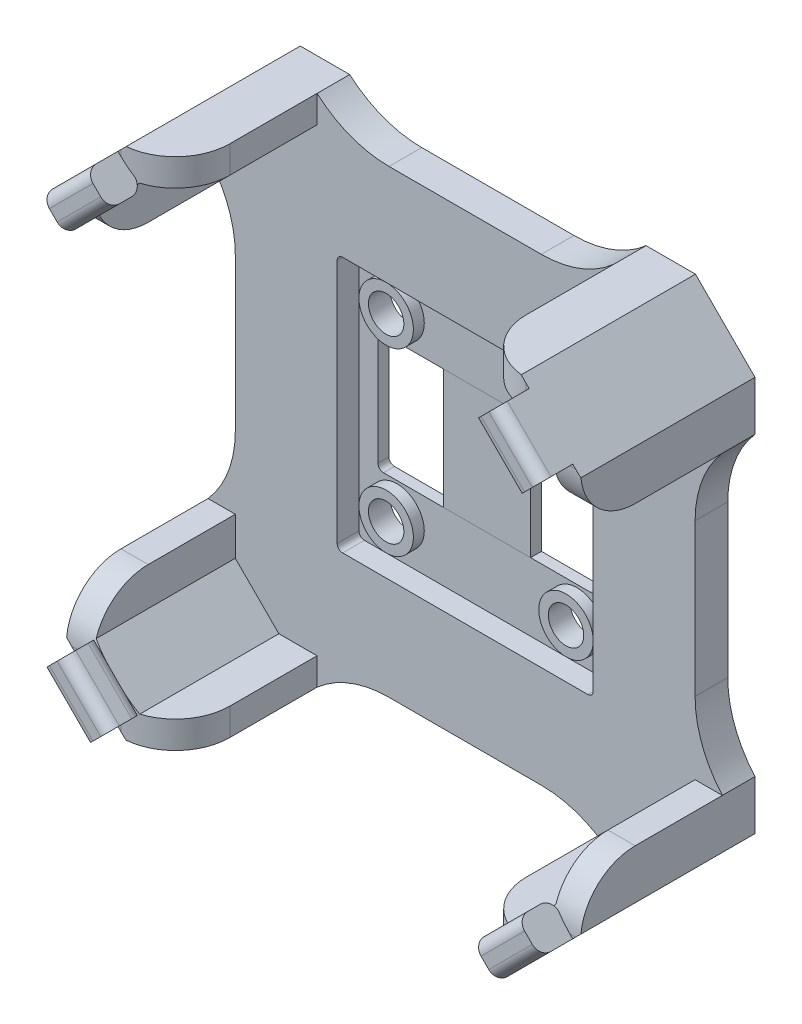
SolidWorks part; units mm, degrees
ref_plane "Front Plane" through (0, 0, 0) normal (0, 0, 1) x (1, 0, 0)
ref_plane "Top Plane" through (0, 0, 0) normal (0, 1, 0) x (1, 0, 0)
ref_plane "Right Plane" through (0, 0, 0) normal (1, 0, 0) x (0, 0, -1)
sketch "Sketch1" plane through (0, 0, 0) normal (0, 0, 1) x (1, 0, 0)
  line L1 (-21.1, 21.1) -> (21.1, 21.1)
  line L2 (-21.1, 21.1) -> (-21.1, -21.1)
  line L3 (-21.1, -21.1) -> (21.1, -21.1)
  line L4 (21.1, 21.1) -> (21.1, -21.1)
  line L5 (0, -21.1) -> (0, 21.1) construction
  line L6 (-21.1, 0) -> (21.1, 0) construction
  line L7 (-10, 5.5) -> (10, 5.5)
  line L8 (-10, 5.5) -> (-10, -5.5)
  line L9 (-10, -5.5) -> (10, -5.5)
  line L10 (10, 5.5) -> (10, -5.5)
  line L11 (0, -5.5) -> (0, 5.5) construction
  line L12 (-10, 0) -> (10, 0) construction
  point P0 (0, 0)
  point P4 (0, 0)
  dimension "D1" = 42.2
  dimension "D2" = 42.2
  dimension "D3" = 20
  dimension "D4" = 11
extrude "Boss-Extrude1" add sketch "Sketch1" along normal blind 3
sketch "Sketch2" plane through (0, 0, 3) normal (0, 0, 1) x (1, 0, 0)
  line L1 (-11.75, 11.75) -> (11.75, 11.75)
  line L2 (-11.75, 11.75) -> (-11.75, -11.75)
  line L3 (-11.75, -11.75) -> (11.75, -11.75)
  line L4 (11.75, 11.75) -> (11.75, -11.75)
  line L5 (0, -11.75) -> (0, 11.75) construction
  line L6 (-11.75, 0) -> (11.75, 0) construction
  point P0 (0, 0)
  dimension "D1" = 23.5
  dimension "D2" = 23.5
extrude "Cut-Extrude1" cut sketch "Sketch2" against normal blind 2
sketch "Sketch3" plane through (0, 0, 0) normal (0, 0, -1) x (-1, 0, 0)
  line L0 (17.1, -21.1) -> (21.1, -17.1)
  line L1 (21.1, -21.1) -> (-21.1, -21.1) construction
  line L2 (21.1, 21.1) -> (21.1, -21.1) construction
  line L4 (21.1, -17.1) -> (21.1, -21.1)
  line L5 (21.1, -21.1) -> (17.1, -21.1)
  line L6 (-21.1, -17.1) -> (-17.1, -21.1)
  line L7 (-17.1, -21.1) -> (-21.1, -21.1)
  line L8 (-21.1, -21.1) -> (-21.1, -17.1)
  line L9 (-17.1, 21.1) -> (-21.1, 17.1)
  line L10 (-21.1, 17.1) -> (-21.1, 21.1)
  line L11 (-21.1, 21.1) -> (-17.1, 21.1)
  line L12 (21.1, 17.1) -> (17.1, 21.1)
  line L13 (17.1, 21.1) -> (21.1, 21.1)
  line L14 (21.1, 21.1) -> (21.1, 17.1)
  point P6 (0, 0)
  dimension "D1" = 4
  dimension "D2" = 5.6569
extrude "Cut-Extrude2" cut sketch "Sketch3" against normal blind 10
sketch "Sketch4" plane through (0, 0, 0) normal (0, 0, -1) x (-1, 0, 0)
  line L0 (21.1, -17.1) -> (21.1, -13.6)
  line L1 (21.1, 17.1) -> (21.1, -17.1) construction
  line L2 (21.1, -13.6) -> (23.6, -13.6)
  line L3 (23.6, -13.6) -> (23.6, -18.1355)
  line L4 (23.6, -18.1355) -> (18.1355, -23.6)
  line L5 (18.1355, -23.6) -> (13.6, -23.6)
  line L6 (13.6, -23.6) -> (13.6, -21.1)
  line L7 (17.1, -21.1) -> (-17.1, -21.1) construction
  line L8 (21.1, -17.1) -> (17.1, -21.1) construction
  line L9 (13.6, -21.1) -> (17.1, -21.1)
  line L10 (21.1, -17.1) -> (17.1, -21.1)
  line L11 (-17.1, -21.1) -> (-13.6, -21.1)
  line L12 (-13.6, -21.1) -> (-13.6, -23.6)
  line L13 (-13.6, -23.6) -> (-18.1355, -23.6)
  line L14 (-18.1355, -23.6) -> (-23.6, -18.1355)
  line L15 (-23.6, -18.1355) -> (-23.6, -13.6)
  line L16 (-23.6, -13.6) -> (-21.1, -13.6)
  line L17 (-21.1, -13.6) -> (-21.1, -17.1)
  line L18 (-17.1, -21.1) -> (-21.1, -17.1)
  line L19 (-21.1, 17.1) -> (-21.1, 13.6)
  line L20 (-21.1, 13.6) -> (-23.6, 13.6)
  line L21 (-23.6, 13.6) -> (-23.6, 18.1355)
  line L22 (-23.6, 18.1355) -> (-18.1355, 23.6)
  line L23 (-18.1355, 23.6) -> (-13.6, 23.6)
  line L24 (-13.6, 23.6) -> (-13.6, 21.1)
  line L25 (-13.6, 21.1) -> (-17.1, 21.1)
  line L26 (-21.1, 17.1) -> (-17.1, 21.1)
  line L27 (17.1, 21.1) -> (13.6, 21.1)
  line L28 (13.6, 21.1) -> (13.6, 23.6)
  line L29 (13.6, 23.6) -> (18.1355, 23.6)
  line L30 (18.1355, 23.6) -> (23.6, 18.1355)
  line L31 (23.6, 18.1355) -> (23.6, 13.6)
  line L32 (23.6, 13.6) -> (21.1, 13.6)
  line L33 (21.1, 13.6) -> (21.1, 17.1)
  line L34 (17.1, 21.1) -> (21.1, 17.1)
  dimension "D1" = 3.5
  dimension "D2" = 2.5
  dimension "D3" = 2.5
  dimension "D4" = 4
extrude "Boss-Extrude2" add sketch "Sketch4" against normal blind 16
fillet "Fillet1" radius 10 8 edges at (-21.1, 13.6, 1.5) (-21.1, -13.6, 1.5) (-13.6, 21.1, 1.5) (13.6, 21.1, 1.5) (21.1, 13.6, 1.5) (21.1, -13.6, 1.5) (13.6, -21.1, 1.5) (-13.6, -21.1, 1.5)
sketch "Sketch5" plane through (0, 0, 1) normal (0, 0, 1) x (1, 0, 0)
  line L0 (6.63, -8.255) -> (-6.63, -8.255) construction
  line L1 (8.255, -6.63) -> (8.255, 6.63) construction
  line L2 (0, -8.255) -> (0, 0) construction
  line L3 (0, 0) -> (8.255, 0) construction
  circle A0 centre (8.255, -8.255) radius 1.625
  circle A1 centre (-8.255, -8.255) radius 1.625
  circle A2 centre (-8.255, 8.255) radius 1.625
  circle A3 centre (8.255, 8.255) radius 1.625
  dimension "D1" = 3.25
  dimension "D3" = 13.26
  dimension "D2" = 4
extrude "Cut-Extrude3" cut sketch "Sketch5" against normal blind 16
sketch "Sketch6" plane through (0, 0, 16) normal (0, 0, 1) x (1, 0, 0)
  line L0 (18.8678, 22.8678) -> (16.7464, 20.7464)
  line L1 (16.7464, 20.7464) -> (20.7464, 16.7464)
  line L2 (20.7464, 16.7464) -> (22.8678, 18.8678)
  line L3 (18.1355, 23.6) -> (23.6, 18.1355) construction
  line L6 (17.1, 21.1) -> (21.1, 17.1) construction
  line L7 (18.8678, 22.8678) -> (22.8678, 18.8678)
  line L8 (21.1, 17.1) -> (17.1, 21.1) construction
  line L9 (22.8678, -18.8678) -> (20.7464, -16.7464)
  line L10 (20.7464, -16.7464) -> (16.7464, -20.7464)
  line L11 (16.7464, -20.7464) -> (18.8678, -22.8678)
  line L12 (22.8678, -18.8678) -> (18.8678, -22.8678)
  line L13 (-18.8678, -22.8678) -> (-16.7464, -20.7464)
  line L14 (-16.7464, -20.7464) -> (-20.7464, -16.7464)
  line L15 (-20.7464, -16.7464) -> (-22.8678, -18.8678)
  line L16 (-18.8678, -22.8678) -> (-22.8678, -18.8678)
  line L17 (-22.8678, 18.8678) -> (-20.7464, 16.7464)
  line L18 (-20.7464, 16.7464) -> (-16.7464, 20.7464)
  line L19 (-16.7464, 20.7464) -> (-18.8678, 22.8678)
  line L20 (-22.8678, 18.8678) -> (-18.8678, 22.8678)
  dimension "D1" = 0.5
  dimension "D2" = 4
extrude "Boss-Extrude3" add sketch "Sketch6" along normal blind 3
fillet "Fillet2" radius 1 4 edges at (18.7464, 18.7464, 16) (-18.7464, 18.7464, 16) (-18.7464, -18.7464, 16) (18.7464, -18.7464, 16)
fillet "Fillet3" radius 5 8 edges at (-22.35, 13.6, 16) (-13.6, 22.35, 16) (-22.35, -13.6, 16) (-13.6, -22.35, 16) (13.6, -22.35, 16) (22.35, -13.6, 16) (22.35, 13.6, 16) (13.6, 22.35, 16)
fillet "Fillet4" radius 1 8 edges at (18.7464, -18.7464, 19) (20.8678, -20.8678, 19) (20.8678, 20.8678, 19) (18.7464, 18.7464, 19) (-18.7464, 18.7464, 19) (-20.8678, 20.8678, 19) (-18.7464, -18.7464, 19) (-20.8678, -20.8678, 19)
fillet "Fillet5" radius 0.5 4 edges at (10, -5.5, 0.5) (-10, 5.5, 0.5) (-10, -5.5, 0.5) (10, 5.5, 0.5)
fillet "Fillet6" radius 0.5 4 edges at (11.75, -11.75, 2) (-11.75, -11.75, 2) (-11.75, 11.75, 2) (11.75, 11.75, 2)
sketch "Sketch7" plane through (0, 0, 1) normal (0, 0, 1) x (1, 0, 0)
  circle A0 centre (8.255, -8.255) radius 2.5
  circle A1 centre (8.255, -8.255) radius 1.625
  circle A2 centre (-8.255, -8.255) radius 2.5
  circle A3 centre (-8.255, -8.255) radius 1.625
  circle A4 centre (-8.255, 8.255) radius 2.5
  circle A5 centre (-8.255, 8.255) radius 1.625
  circle A6 centre (8.255, 8.255) radius 2.5
  circle A7 centre (8.255, 8.255) radius 1.625
  dimension "D1" = 5
  dimension "D2" = 4
extrude "Boss-Extrude4" add sketch "Sketch7" along normal blind 1
sketch "Sketch8" plane through (0, 0, 0) normal (0, 0, -1) x (-1, 0, 0)
  line L0 (9.5, -5.5) -> (-9.5, -5.5) construction
  line L1 (-4, 5.5) -> (4, 5.5)
  line L2 (-4, 5.5) -> (-4, -5.5)
  line L3 (-4, -5.5) -> (4, -5.5)
  line L4 (4, 5.5) -> (4, -5.5)
  line L5 (0, -5.5) -> (0, 5.5) construction
  line L6 (-4, 0) -> (4, 0) construction
  point P0 (0, 0)
  dimension "D1" = 8
extrude "Boss-Extrude5" add sketch "Sketch8" against normal blind 1 separate body
